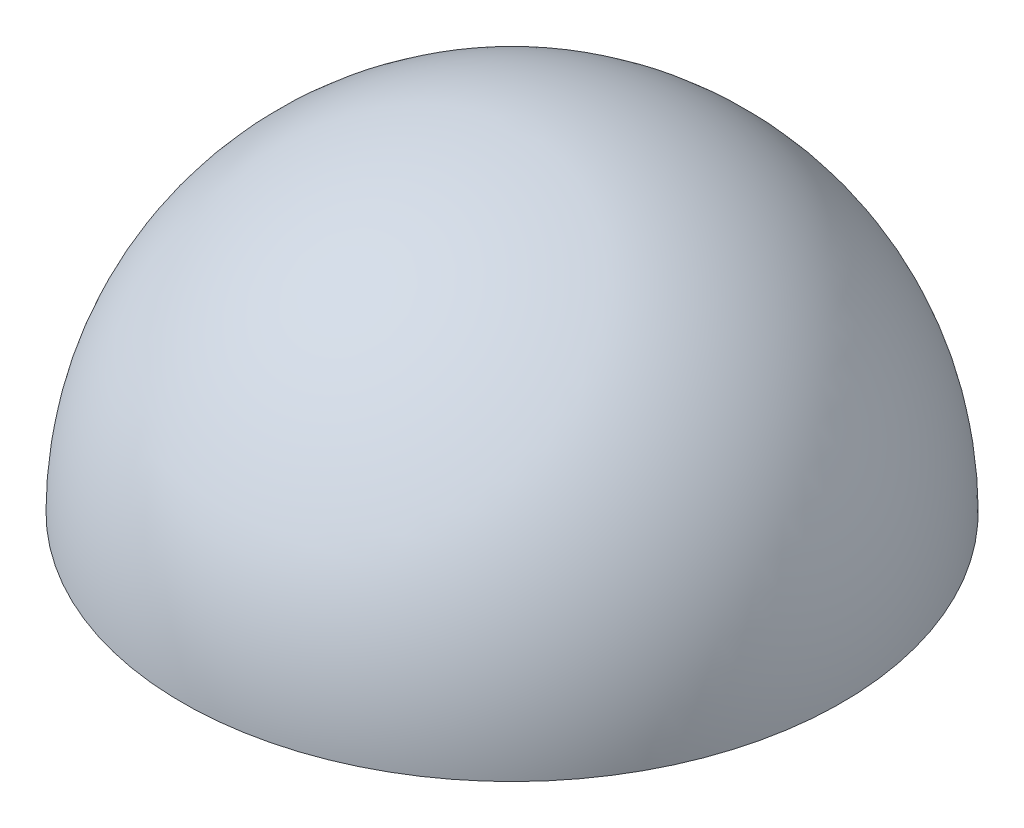
SolidWorks part; units mm, degrees
ref_plane "正面" through (0, 0, 0) normal (0, 0, 1) x (1, 0, 0)
ref_plane "平面" through (0, 0, 0) normal (0, 1, 0) x (1, 0, 0)
ref_plane "右側面" through (0, 0, 0) normal (1, 0, 0) x (0, 0, -1)
sketch "Sketch2" plane through (0, 0, 0) normal (0, 1, 0) x (1, 0, 0)
  circle A0 centre (0, 0) radius 2.25
extrude "Boss-Extrude1" add sketch "Sketch2" along normal blind 0.1
dome "Dome1" faces to dome 1 distance 2.25 reverse direction no elliptical dome no face at (0, 0.1, 2.25) parameters "D1"=2.25
sketch "Sketch4" plane through (0, 0, 0) normal (0, -1, 0) x (1, 0, 0)
  circle A0 centre (0, 0) radius 2.25
extrude "Cut-Extrude1" cut sketch "Sketch4" against normal blind 0.1
shell "Shell1" thickness 0.1 removed face at (0, 0.1, -2.25)
